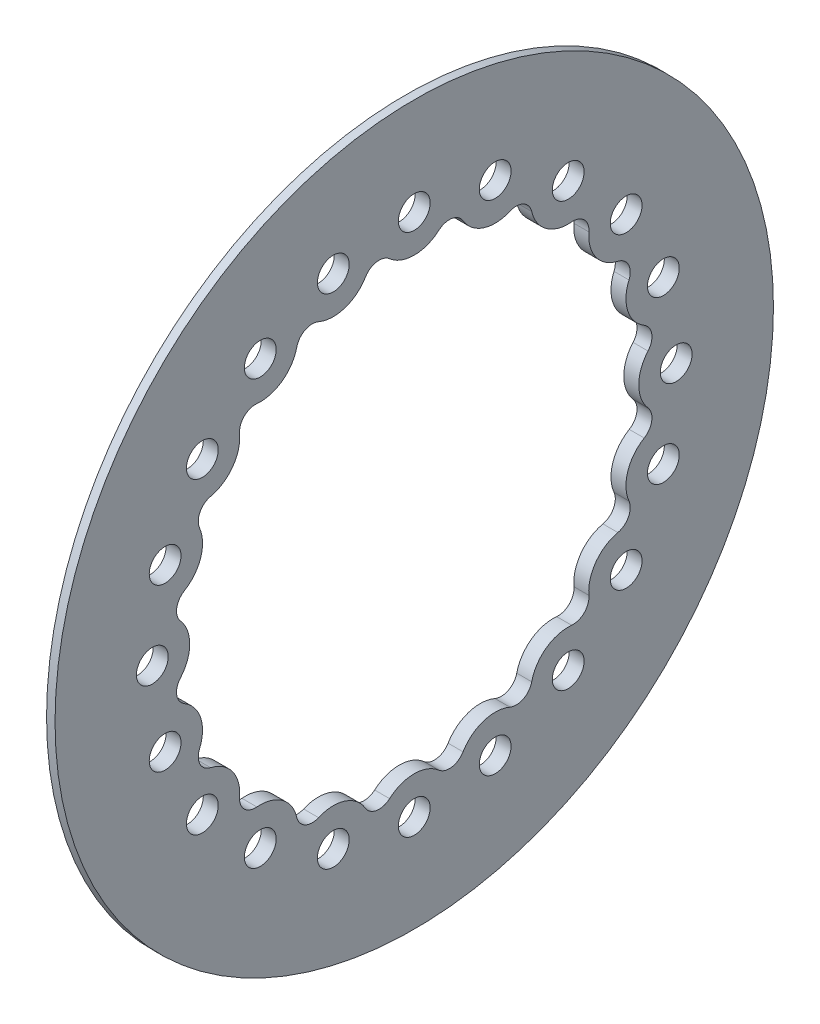
SolidWorks part; units mm, degrees
material "Plain Carbon Steel"
ref_plane "Front Plane" through (0, 0, 0) normal (0, 0, 1) x (1, 0, 0)
ref_plane "Top Plane" through (0, 0, 0) normal (0, 1, 0) x (1, 0, 0)
ref_plane "Right Plane" through (0, 0, 0) normal (1, 0, 0) x (0, 0, -1)
sketch "Sketch1" plane through (0, 0, 0) normal (1, 0, 0) x (0, 0, -1)
  circle A0 centre (0, 0) radius 96
  circle A1 centre (0, 0) radius 60
  dimension "D1" = 192
  dimension "D2" = 120
extrude "Boss-Extrude1" add sketch "Sketch1" along normal mid plane 4
sketch "Sketch2" plane through (2, 0, 0) normal (1, 0, 0) x (0, 0, -1)
  line L0 (0, 80) -> (0, 60) construction
  line L1 (10.4902, 55.1756) -> (-0.2316, 55.1756)
  line L2 (9.3891, 59.2805) -> (0, 0) construction
  line L3 (-9.3891, 59.2805) -> (0, 0) construction
  line L4 (-10.4902, 55.1756) -> (-0.2316, 55.1756)
  circle A0 centre (0, 70) radius 4.25
  arc A1 (-6.5889, 62.4776) -> (6.5889, 62.4776) centre (0, 70) ccw
  arc A3 (6.5889, 62.4776) -> (10.4902, 55.1756) centre (9.3891, 59.2805) cw
  arc A4 (-6.5889, 62.4776) -> (-10.4902, 55.1756) centre (-9.3891, 59.2805) ccw
  circle A5 centre (0, 0) radius 60 construction
  dimension "D1" = 8.5
  dimension "D2" = 70
  dimension "D3" = 18
extrude "Cut-Extrude1" cut sketch "Sketch2" against normal through all
pattern_circular "CirPattern1" count 20 over 360 about axis through (2, 0, 0) along (-1, 0, 0) of "Cut-Extrude1"
ref_axis "Axis1" through (2, 0, 0) along (-1, 0, 0)
chamfer "Chamfer1" distance 3 angle 30 1 edges at (-2, 0, -96) first distance on face at (-2, 67.8873, 17.5892)
